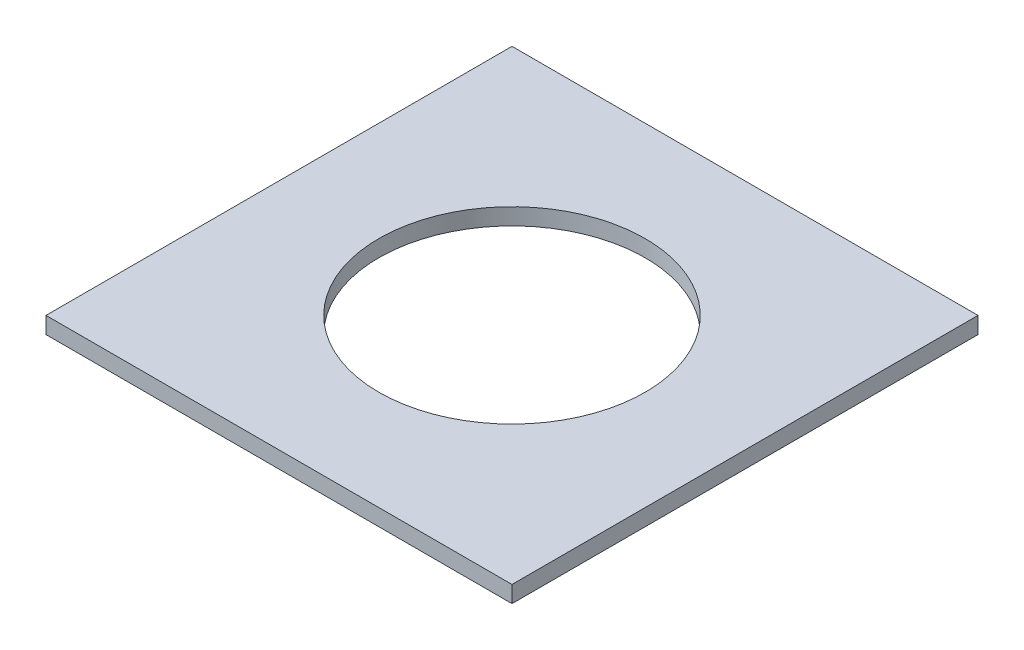
SolidWorks part; units mm, degrees
material "Maple"
ref_plane "Front" through (0, 0, 0) normal (0, 0, 1) x (1, 0, 0)
ref_plane "Top" through (0, 0, 0) normal (0, 1, 0) x (1, 0, 0)
ref_plane "Right" through (0, 0, 0) normal (1, 0, 0) x (0, 0, -1)
sketch "Sketch1" plane through (0, 0, 0) normal (0, 1, 0) x (1, 0, 0)
  line L1 (-7, -7) -> (7, -7)
  line L2 (-7, -7) -> (-7, 7)
  line L3 (-7, 7) -> (7, 7)
  line L4 (7, -7) -> (7, 7)
  line L5 (-7, -7) -> (7, 7) construction
  line L6 (-7, 7) -> (7, -7) construction
  circle A0 centre (0, 0) radius 4
  point P0 (0, 0)
  dimension "D3" = 8
  dimension "D1" = 14
  dimension "D2" = 14
extrude "Boss-Extrude1" add sketch "Sketch1" along normal blind 0.5
